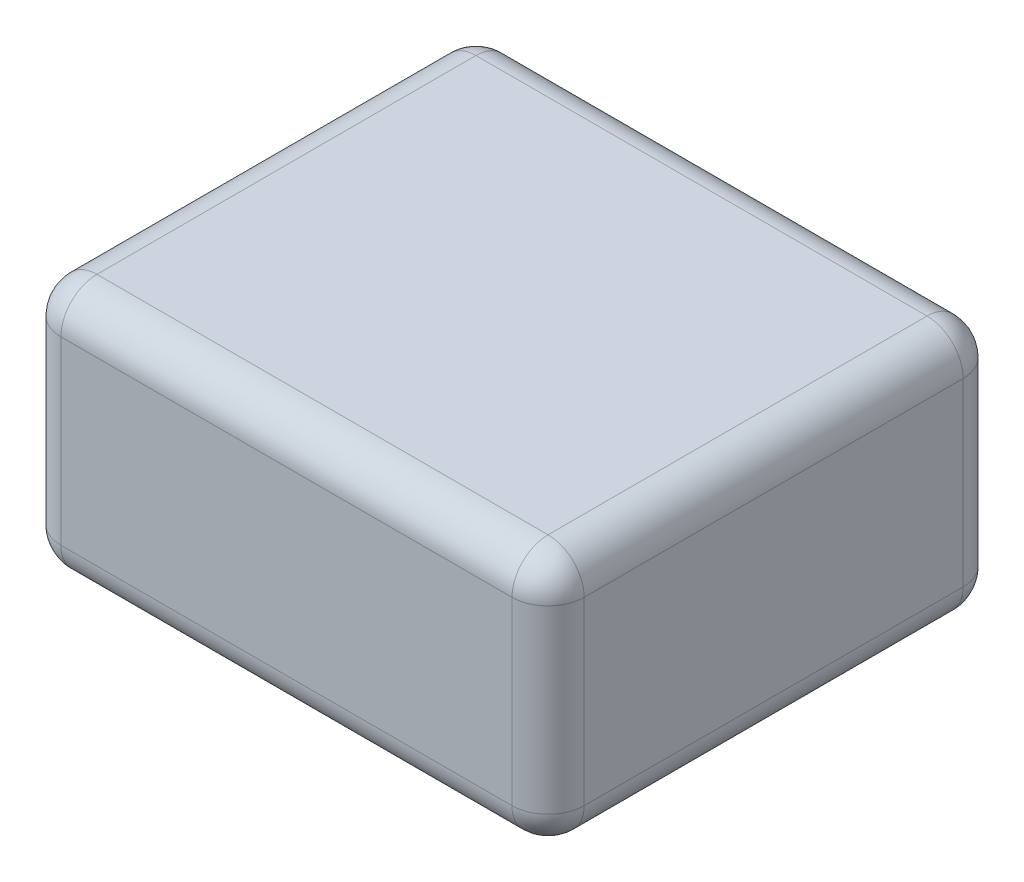
SolidWorks part; units mm, degrees
ref_plane "Front" through (0, 0, 0) normal (0, 0, 1) x (1, 0, 0)
ref_plane "Top" through (0, 0, 0) normal (0, 1, 0) x (1, 0, 0)
ref_plane "Right" through (0, 0, 0) normal (1, 0, 0) x (0, 0, -1)
ref_axis "Center Axis" through (0, 0, -88.99) along (0, 0, 1)
sketch "Sketch1" plane through (0, 0, 0) normal (0, 1, 0) x (1, 0, 0)
  line L1 (-92.075, 79.375) -> (92.075, 79.375)
  line L2 (-92.075, 79.375) -> (-92.075, -79.375)
  line L3 (-92.075, -79.375) -> (92.075, -79.375)
  line L4 (92.075, 79.375) -> (92.075, -79.375)
  line L5 (-92.075, 79.375) -> (92.075, -79.375) construction
  line L6 (-92.075, -79.375) -> (92.075, 79.375) construction
  point P0 (0, 0)
  dimension "D1" = 184.15
  dimension "D2" = 158.75
extrude "Boss-Extrude1" add sketch "Sketch1" along normal blind 88.9
fillet "Fillet1" radius 12.7 12 edges at (-92.075, 0, 0) (-92.075, 44.45, -79.375) (0, 0, -79.375) (92.075, 44.45, -79.375) (92.075, 0, 0) (-92.075, 88.9, 0) (0, 88.9, -79.375) (92.075, 88.9, 0) (-92.075, 44.45, 79.375) (0, 88.9, 79.375) (92.075, 44.45, 79.375) (0, 0, 79.375)
